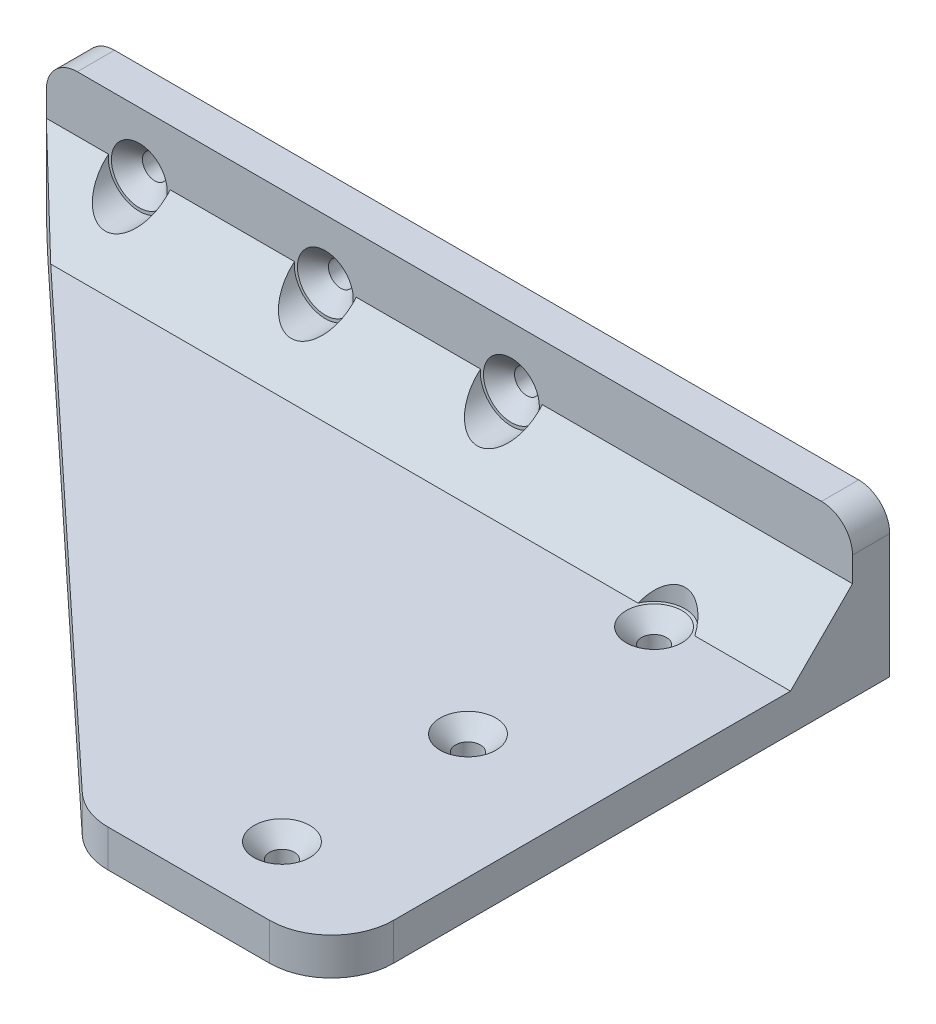
SolidWorks part; units mm, degrees
ref_plane "Front" through (0, 0, 0) normal (0, 0, 1) x (1, 0, 0)
ref_plane "Top" through (0, 0, 0) normal (0, 1, 0) x (1, 0, 0)
ref_plane "Right" through (0, 0, 0) normal (1, 0, 0) x (0, 0, -1)
sketch "Esquisse1" plane through (0, 0, 0) normal (0, 0, 1) x (1, 0, 0)
  line L1 (0, 0) -> (90, 0)
  line L2 (0, 0) -> (0, 25)
  line L3 (0, 25) -> (90, 25)
  line L4 (90, 0) -> (90, 25)
  dimension "D1" = 90
  dimension "D2" = 25
extrude "Boss.-Extru.1" add sketch "Esquisse1" along normal blind 6
sketch "Esquisse2" plane through (90, 0, 0) normal (1, 0, 0) x (0, 0, -1)
  line L0 (0, 0) -> (-90, 0)
  line L1 (-90, 0) -> (-90, 6)
  line L2 (-90, 6) -> (0, 6)
  line L3 (0, 0) -> (0, 25) construction
  line L4 (0, 6) -> (0, 0)
  dimension "D1" = 6
  dimension "D2" = 90
extrude "Boss.-Extru.2" add sketch "Esquisse2" along normal blind 40
sketch "Esquisse3" plane through (0, 6, 0) normal (0, 1, 0) x (1, 0, 0)
  line L0 (130, 0) -> (130, -90) construction
  line L1 (90, 0) -> (130, 0)
  line L2 (90, 0) -> (90, -6)
  line L3 (90, -6) -> (130, -6)
  line L4 (130, 0) -> (130, -6)
  line L5 (90, -6) -> (0, -6) construction
extrude "Boss.-Extru.3" add sketch "Esquisse3" along normal up to surface (19 mm away) up to face at (45, 25, 3)
sketch "Esquisse4" plane through (0, 0, 0) normal (0, -1, 0) x (1, 0, 0)
  line L0 (0, 6) -> (90, 90)
  line L1 (90, 90) -> (90, 6)
  line L2 (90, 6) -> (0, 6)
extrude "Boss.-Extru.4" add sketch "Esquisse4" against normal up to vertex (6 mm away) up to point (90, 6, 6)
sketch "Esquisse5" plane through (0, 0, 6) normal (0, 0, 1) x (1, 0, 0)
  line L0 (0, 15.5) -> (90, 15.5) construction
  line L1 (0, 25) -> (0, 6) construction
  line L2 (90, 15.5) -> (90, 6) construction
  line L3 (45, 15.5) -> (45, 22.4998) construction
  circle A0 centre (45, 15.5) radius 2
  circle A1 centre (15, 15.5) radius 2
  circle A2 centre (75, 15.5) radius 2
  dimension "D1" = 4
  dimension "D2" = 30
extrude "Enlèv. mat.-Extru.1" cut sketch "Esquisse5" against normal through all
sketch "Esquisse6" plane through (0, 6, 0) normal (0, 1, 0) x (1, 0, 0)
  line L0 (110, -90) -> (110, -6) construction
  line L1 (130, -90) -> (90, -90) construction
  line L2 (0, -6) -> (130, -6) construction
  line L3 (110, -48) -> (97.24, -48) construction
  circle A0 centre (110, -48) radius 2
  circle A1 centre (110, -18) radius 2
  circle A2 centre (110, -78) radius 2
  dimension "D1" = 4
  dimension "D2" = 30
extrude "Enlèv. mat.-Extru.2" cut sketch "Esquisse6" against normal through all both and the other way through all
chamfer "Chanfrein1" distance 10 angle 45 1 edges at (65, 6, 6)
sketch "Esquisse7" plane through (0, 0, 6) normal (0, 0, 1) x (1, 0, 0)
  circle A0 centre (45, 15.5) radius 5
  circle A1 centre (15, 15.5) radius 5
  circle A2 centre (75, 15.5) radius 5
  dimension "D1" = 10
extrude "Enlèv. mat.-Extru.3" cut sketch "Esquisse7" along normal through all
sketch "Esquisse8" plane through (0, 6, 0) normal (0, 1, 0) x (1, 0, 0)
  circle A0 centre (110, -18) radius 5
  dimension "D1" = 10
extrude "Enlèv. mat.-Extru.4" cut sketch "Esquisse8" along normal through all
chamfer "Chanfrein3" distance 2.5 angle 45 6 edges at (110, 6, 76) (110, 6, 46) (110, 6, 16) (73, 15.5, 6) (47, 15.5, 6) (17, 15.5, 6)
fillet "Congé1" radius 10 2 edges at (130, 3, 90) (90, 3, 90)
fillet "Congé2" radius 5 3 edges at (0, 0, 3) (0, 25, 3) (130, 25, 3)
